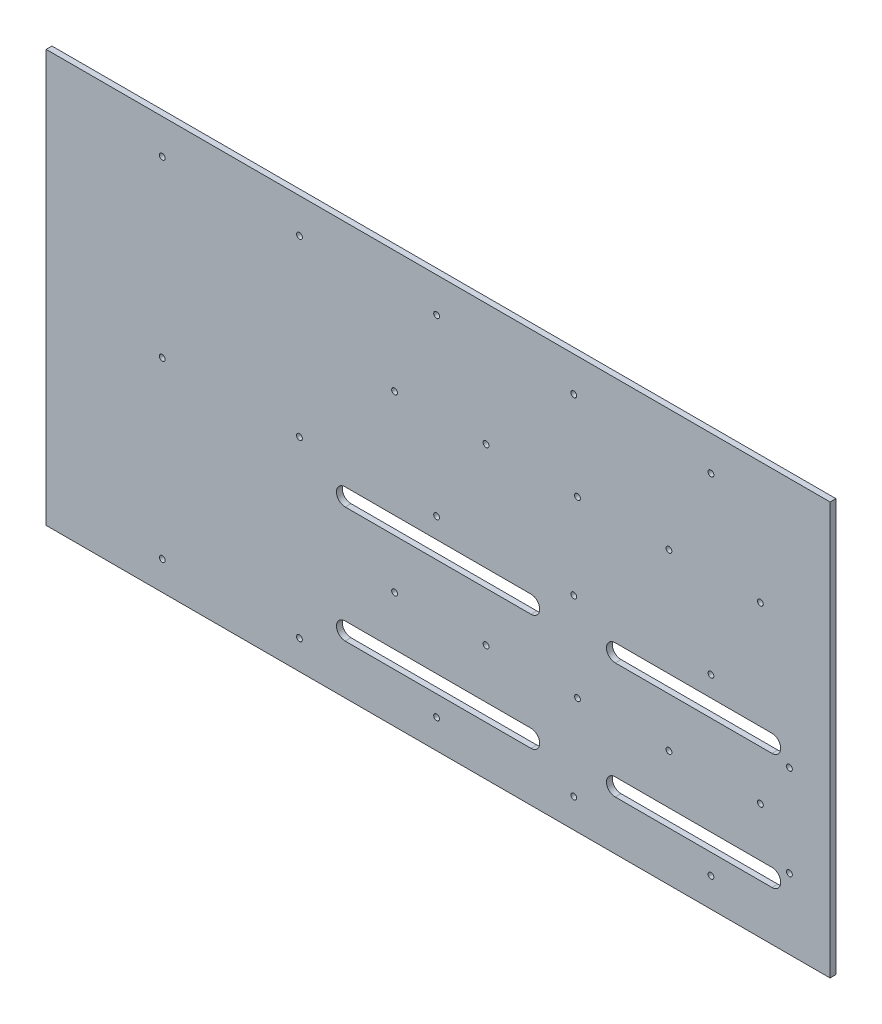
SolidWorks part; units mm, degrees
ref_plane "Front Plane" through (0, 0, 0) normal (0, 0, 1) x (1, 0, 0)
ref_plane "Top Plane" through (0, 0, 0) normal (0, 1, 0) x (1, 0, 0)
ref_plane "Right Plane" through (0, 0, 0) normal (1, 0, 0) x (0, 0, -1)
sketch "Sketch1" plane through (0, 0, 0) normal (0, 0, 1) x (1, 0, 0)
  line L1 (-428.625, 225.425) -> (428.625, 225.425)
  line L2 (-428.625, 225.425) -> (-428.625, -225.425)
  line L3 (-428.625, -225.425) -> (428.625, -225.425)
  line L4 (428.625, 225.425) -> (428.625, -225.425)
  point P4 (0, -225.425)
  point P6 (-428.625, 0)
  dimension "D1" = 857.25
  dimension "D2" = 450.85
extrude "Boss-Extrude1" add sketch "Sketch1" along normal blind 6.35
sketch "Sketch4" plane through (0, 0, 6.35) normal (0, 0, 1) x (1, 0, 0)
  line L0 (-47.575, 92.075) -> (52.425, 92.075) construction
  line L1 (152.425, 92.075) -> (52.425, 92.075) construction
  line L2 (152.425, 92.075) -> (252.425, 92.075) construction
  line L3 (252.425, 92.075) -> (352.425, 92.075) construction
  line L4 (428.625, -225.425) -> (428.625, 225.425) construction
  line L6 (-47.575, -98.425) -> (52.425, -98.425) construction
  line L7 (152.425, -98.425) -> (52.425, -98.425) construction
  line L8 (152.425, -98.425) -> (252.425, -98.425) construction
  line L9 (252.425, -98.425) -> (352.425, -98.425) construction
  line L10 (-428.625, -225.425) -> (428.625, -225.425) construction
  circle A0 centre (352.425, 92.075) radius 3.175
  circle A1 centre (252.425, 92.075) radius 3.175
  circle A2 centre (152.425, 92.075) radius 3.175
  circle A3 centre (52.425, 92.075) radius 3.175
  circle A4 centre (-47.575, 92.075) radius 3.175
  circle A5 centre (352.425, -98.425) radius 3.175
  circle A6 centre (252.425, -98.425) radius 3.175
  circle A7 centre (152.425, -98.425) radius 3.175
  circle A8 centre (52.425, -98.425) radius 3.175
  circle A9 centre (-47.575, -98.425) radius 3.175
  point P24 (0, 0)
  dimension "D1" = 6.35
  dimension "D2" = 100
  dimension "D3" = 76.2
  dimension "D4" = 127
  dimension "D5" = 190.5
extrude "Cut-Extrude3" cut sketch "Sketch4" against normal through all
sketch "Sketch2" plane through (0, 0, 6.35) normal (0, 0, 1) x (1, 0, 0)
  line L5 (428.625, -225.425) -> (428.625, 225.425) construction
  line L6 (-101.6, -161.925) -> (101.6, -161.925) construction
  line L7 (-101.6, -152.4) -> (101.6, -152.4)
  line L8 (-101.6, -171.45) -> (101.6, -171.45)
  line L9 (193.675, -161.925) -> (365.125, -161.925) construction
  line L10 (193.675, -152.4) -> (365.125, -152.4)
  line L11 (193.675, -171.45) -> (365.125, -171.45)
  line L12 (-301.6262, -193.675) -> (-151.6262, -193.675) construction
  line L15 (365.125, -34.925) -> (193.675, -34.925) construction
  line L16 (365.125, -44.45) -> (193.675, -44.45)
  line L17 (365.125, -25.4) -> (193.675, -25.4)
  line L18 (-151.6262, -193.675) -> (-1.6262, -193.675) construction
  line L21 (101.6, -34.925) -> (-101.6, -34.925) construction
  line L22 (101.6, -44.45) -> (-101.6, -44.45)
  line L23 (101.6, -25.4) -> (-101.6, -25.4)
  line L24 (184.15, -161.925) -> (111.125, -161.925) construction
  line L25 (-1.6262, -193.675) -> (148.3738, -193.675) construction
  line L26 (148.3738, -193.675) -> (298.3738, -193.675) construction
  line L27 (-301.6262, -193.675) -> (-428.625, -193.675) construction
  line L28 (-428.625, 225.425) -> (-428.625, -225.425) construction
  line L29 (298.3738, -193.675) -> (428.625, -193.675) construction
  line L30 (-301.6262, -3.175) -> (-151.6262, -3.175) construction
  line L31 (-151.6262, -3.175) -> (-1.6262, -3.175) construction
  line L32 (-1.6262, -3.175) -> (148.3738, -3.175) construction
  line L33 (148.3738, -3.175) -> (298.3738, -3.175) construction
  line L34 (298.3738, 187.325) -> (148.3738, 187.325) construction
  line L35 (148.3738, 187.325) -> (-1.6262, 187.325) construction
  line L36 (-1.6262, 187.325) -> (-151.6262, 187.325) construction
  line L37 (-151.6262, 187.325) -> (-301.6262, 187.325) construction
  arc A5 (-101.6, -152.4) -> (-101.6, -171.45) centre (-101.6, -161.925) ccw
  arc A6 (101.6, -171.45) -> (101.6, -152.4) centre (101.6, -161.925) ccw
  arc A7 (193.675, -152.4) -> (193.675, -171.45) centre (193.675, -161.925) ccw
  arc A8 (365.125, -171.45) -> (365.125, -152.4) centre (365.125, -161.925) ccw
  arc A11 (365.125, -44.45) -> (365.125, -25.4) centre (365.125, -34.925) ccw
  arc A12 (193.675, -25.4) -> (193.675, -44.45) centre (193.675, -34.925) ccw
  arc A15 (101.6, -44.45) -> (101.6, -25.4) centre (101.6, -34.925) ccw
  arc A16 (-101.6, -25.4) -> (-101.6, -44.45) centre (-101.6, -34.925) ccw
  circle A17 centre (298.3738, -193.675) radius 3.175
  circle A18 centre (148.3738, -193.675) radius 3.175
  circle A19 centre (-1.6262, -193.675) radius 3.175
  circle A20 centre (-151.6262, -193.675) radius 3.175
  circle A21 centre (-301.6262, -193.675) radius 3.175
  circle A22 centre (298.3738, -3.175) radius 3.175
  circle A23 centre (148.3738, -3.175) radius 3.175
  circle A24 centre (-1.6262, -3.175) radius 3.175
  circle A25 centre (-151.6262, -3.175) radius 3.175
  circle A26 centre (-301.6262, -3.175) radius 3.175
  circle A27 centre (298.3738, 187.325) radius 3.175
  circle A28 centre (148.3738, 187.325) radius 3.175
  circle A29 centre (-1.6262, 187.325) radius 3.175
  circle A30 centre (-151.6262, 187.325) radius 3.175
  circle A31 centre (-301.6262, 187.325) radius 3.175
  point P16 (0, -161.925)
  point P23 (279.4, -161.925)
  point P28 (184.15, -161.925)
  point P29 (374.65, -161.925)
  point P42 (279.4, -34.925)
  point P54 (0, -34.925)
  point P67 (374.65, -34.925)
  point P81 (0, 0)
  dimension "D5" = 19.05
  dimension "D6" = 190.5
  dimension "D12" = 6.35
  dimension "D3" = 95.25
  dimension "D2" = 190.5
  dimension "D8" = 317.5
  dimension "D10" = 63.5
  dimension "D11" = 203.2
  dimension "D13" = 150
  dimension "D14" = 31.75
  dimension "D15" = 130.2512
  dimension "D16" = 31.75
  dimension "D17" = 190.5
extrude "Cut-Extrude1" cut sketch "Sketch2" against normal through all
sketch "Sketch3" plane through (0, 0, 6.35) normal (0, 0, 1) x (1, 0, 0)
  line L0 (384.175, -48.425) -> (384.175, -148.425) construction
  line L1 (384.175, -3.175) -> (384.175, -48.425) construction
  line L2 (298.3738, -3.175) -> (428.625, -3.175) construction
  line L4 (384.175, -148.425) -> (384.175, -193.675) construction
  line L6 (428.625, -225.425) -> (428.625, 225.425) construction
  line L7 (298.3738, -193.675) -> (428.625, -193.675) construction
  circle A0 centre (384.175, -148.425) radius 3.175
  circle A1 centre (384.175, -48.425) radius 3.175
  point P6 (384.175, 15.875)
  point P11 (384.175, -196.1609)
  point P12 (384.175, -184.125)
  point P17 (0, 0)
  point P18 (384.175, -48.4553)
  point P19 (384.175, -187.325)
  dimension "D1" = 6.35
  dimension "D2" = 100
  dimension "D3" = 44.45
extrude "Cut-Extrude2" cut sketch "Sketch3" against normal through all
